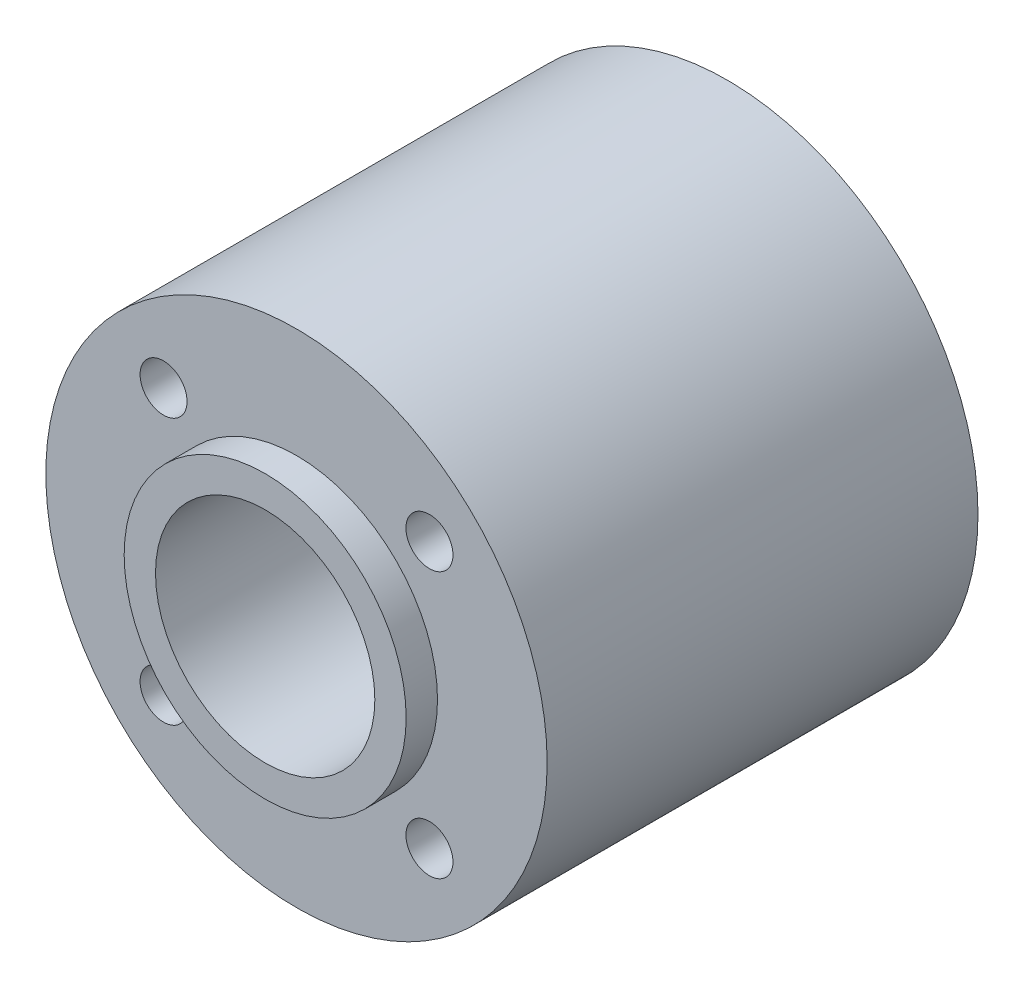
SolidWorks part; units mm, degrees
material "Nylon 101"
ref_plane "Front Plane" through (0, 0, 0) normal (0, 0, 1) x (1, 0, 0)
ref_plane "Top Plane" through (0, 0, 0) normal (0, 1, 0) x (1, 0, 0)
ref_plane "Right Plane" through (0, 0, 0) normal (1, 0, 0) x (0, 0, -1)
sketch "Sketch1" plane through (0, 0, 0) normal (0, 0, 1) x (1, 0, 0)
  line L0 (0, 0) -> (0, 16) construction
  line L1 (0, 0) -> (-11.3137, 11.3137) construction
  circle A1 centre (0, 0) radius 7
  circle A2 centre (0, 0) radius 9
  circle A3 centre (0, 0) radius 16
  circle A4 centre (0, 0) radius 12 construction
  circle A5 centre (-8.4853, 8.4853) radius 1.5
  circle A6 centre (8.4853, 8.4853) radius 1.5
  circle A7 centre (8.4853, -8.4853) radius 1.5
  circle A8 centre (-8.4853, -8.4853) radius 1.5
  point P17 (0, 0)
  dimension "D1" = 12
  dimension "D2" = 14
  dimension "D3" = 18
  dimension "D4" = 32
  dimension "D5" = 24
  dimension "D7" = 3
  dimension "D6" = 45
  dimension "D8" = 12
  dimension "D10" = 8.4853
  dimension "D9" = 4
extrude "Boss-Extrude1" add sketch "Sketch1" along normal blind 27.5 contours A3 A7 A6 A5 A2 | A2 A1 region at (-8.7454, 0, 0) region at (-15.5475, 0, 0)
extrude "Boss-Extrude2" add sketch "Sketch1<3>" along normal blind 29.5 contours A2 A1 region at (-8.7454, 0, 0)
sketch "Sketch1<3>" plane through (0, 0, 0) normal (0, 0, 1) x (1, 0, 0) same geometry as "Sketch1"
extrude "Boss-Extrude3" add sketch "Sketch1<4>" against normal blind 2 contours A2 A1 region at (-8.7454, 0, 0)
sketch "Sketch1<4>" plane through (0, 0, 0) normal (0, 0, 1) x (1, 0, 0) same geometry as "Sketch1"
